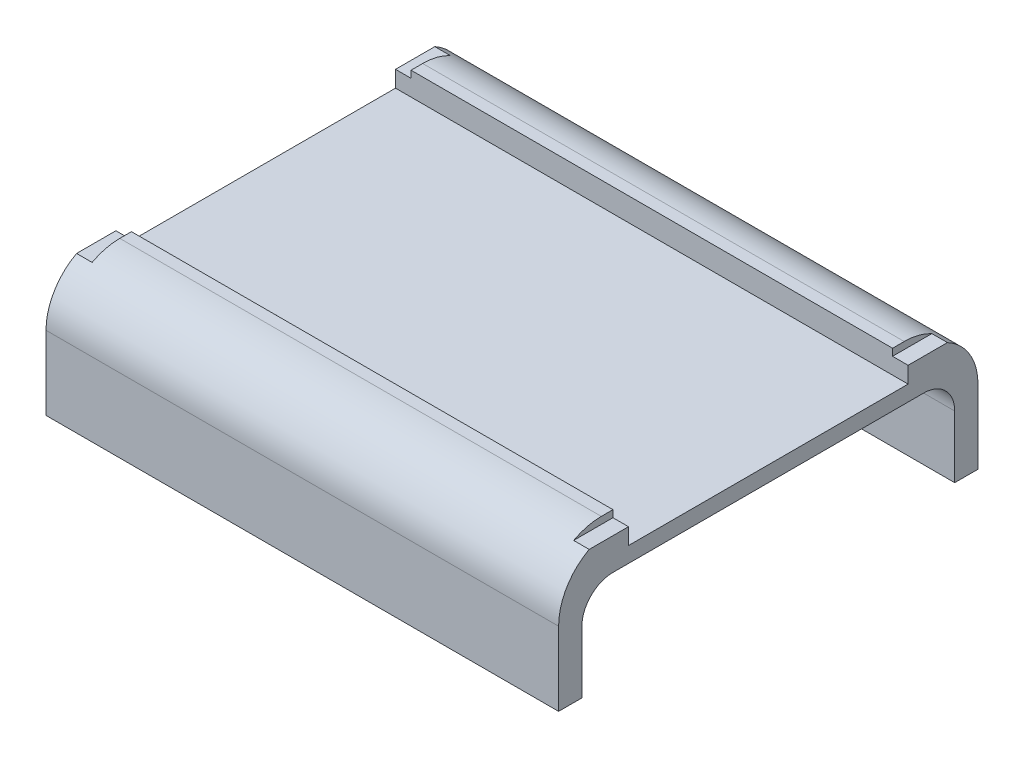
SolidWorks part; units mm, degrees
material "ABS"
ref_plane "Front Plane" through (0, 0, 0) normal (0, 0, 1) x (1, 0, 0)
ref_plane "Top Plane" through (0, 0, 0) normal (0, 1, 0) x (1, 0, 0)
ref_plane "Right Plane" through (0, 0, 0) normal (1, 0, 0) x (0, 0, -1)
sketch "Sketch1" plane through (0, 0, 0) normal (0, 1, 0) x (1, 0, 0)
  line L1 (0, 0) -> (167.64, 0)
  line L2 (0, 0) -> (0, 137.16)
  line L3 (0, 137.16) -> (167.64, 137.16)
  line L4 (167.64, 0) -> (167.64, 137.16)
  dimension "D1" = 137.16
  dimension "D2" = 167.64
extrude "Boss-Extrude1" add sketch "Sketch1" along normal blind 12.7
ref_plane "Plane1" through (0, 12.7, 0) normal (0, 1, 0) x (1, 0, 0)
sketch "Sketch2" plane through (0, 12.7, 0) normal (0, 1, 0) x (1, 0, 0)
  line L0 (0, 137.16) -> (0, 0) construction
  line L1 (0, 114.3) -> (167.64, 114.3)
  line L2 (0, 114.3) -> (0, 22.86)
  line L3 (0, 22.86) -> (167.64, 22.86)
  line L4 (167.64, 114.3) -> (167.64, 22.86)
  line L5 (167.64, 0) -> (167.64, 137.16) construction
  line L6 (167.64, 137.16) -> (0, 137.16) construction
  line L7 (0, 0) -> (167.64, 0) construction
  dimension "D1" = 22.86
  dimension "D2" = 22.86
extrude "Cut-Extrude1" cut sketch "Sketch2" against normal blind 7.62
sketch "Sketch3" plane through (0, 12.7, 0) normal (0, 1, 0) x (1, 0, 0)
  line L0 (167.64, 114.3) -> (0, 114.3) construction
  line L1 (0, 137.16) -> (5.08, 137.16)
  line L2 (0, 137.16) -> (0, 114.3)
  line L3 (0, 114.3) -> (5.08, 114.3)
  line L4 (5.08, 137.16) -> (5.08, 114.3)
  line L5 (0, 0) -> (167.64, 0) construction
  line L6 (167.64, 137.16) -> (162.56, 137.16)
  line L7 (167.64, 137.16) -> (167.64, 114.3)
  line L8 (167.64, 114.3) -> (162.56, 114.3)
  line L9 (162.56, 137.16) -> (162.56, 114.3)
  line L10 (167.64, 22.86) -> (162.56, 22.86)
  line L11 (167.64, 22.86) -> (167.64, 0)
  line L12 (167.64, 0) -> (162.56, 0)
  line L13 (162.56, 22.86) -> (162.56, 0)
  line L15 (0, 22.86) -> (5.08, 22.86)
  line L16 (0, 22.86) -> (0, 0)
  line L17 (0, 0) -> (5.08, 0)
  line L18 (5.08, 22.86) -> (5.08, 0)
  dimension "D1" = 5.08
  dimension "D2" = 5.08
extrude "Cut-Extrude2" cut sketch "Sketch3" against normal blind 2.286
sketch "Sketch4" plane through (0, 0, 0) normal (0, -1, 0) x (1, 0, 0)
  line L1 (167.64, -137.16) -> (0, -137.16) construction
  line L2 (0, -137.16) -> (0, 0) construction
  circle A0 centre (81.788, -15.494) radius 6.35
  circle A1 centre (81.788, -15.494) radius 4.826
  circle A2 centre (81.788, -121.92) radius 6.35
  circle A3 centre (81.788, -121.92) radius 4.826
  dimension "D1" = 15.24
  dimension "D3" = 12.7
  dimension "D4" = 9.652
  dimension "D5" = 12.7
  dimension "D6" = 9.652
  dimension "D2" = 106.426
  dimension "D7" = 81.788
extrude "Boss-Extrude2" add sketch "Sketch4" along normal blind 30.4648
sketch "Sketch5" plane through (0, 0, 0) normal (0, -1, 0) x (1, 0, 0)
  line L0 (0, -137.16) -> (0, 0) construction
  line L1 (167.64, -137.16) -> (0, -137.16)
  line L2 (167.64, -137.16) -> (167.64, -129.54)
  line L3 (167.64, -129.54) -> (0, -129.54)
  line L4 (0, -137.16) -> (0, -129.54)
  line L6 (167.64, 0) -> (0, 0)
  line L7 (167.64, 0) -> (167.64, -7.62)
  line L8 (167.64, -7.62) -> (0, -7.62)
  line L9 (0, 0) -> (0, -7.62)
  dimension "D1" = 7.62
  dimension "D2" = 7.62
extrude "Boss-Extrude3" add sketch "Sketch5" along normal blind 30.4648
fillet "Fillet1" radius 19.05 2 edges at (83.82, 12.7, 0) (83.82, 12.7, -137.16)
fillet "Fillet2" radius 10.16 2 edges at (83.82, 0, -7.62) (83.82, 0, -129.54)
